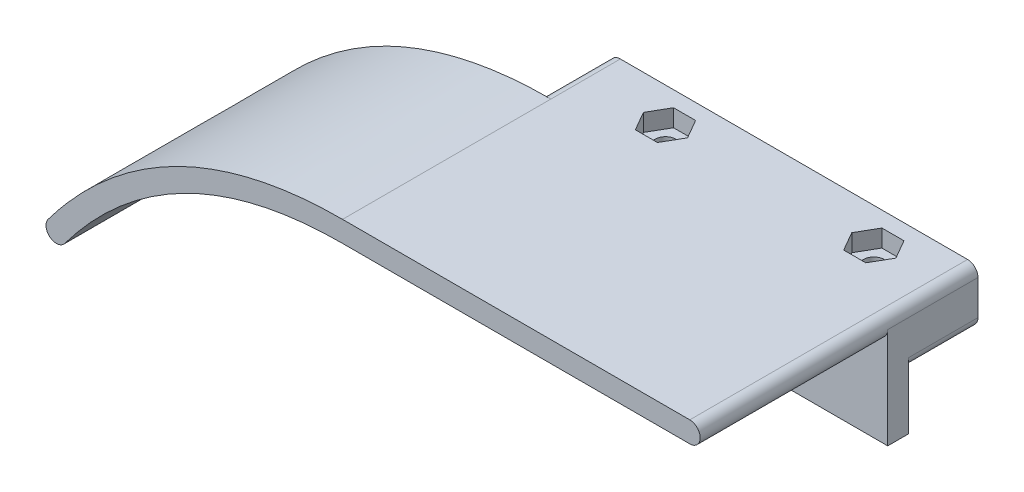
SolidWorks part; units mm, degrees
ref_plane "前视基准面" through (0, 0, 0) normal (0, 0, 1) x (1, 0, 0)
ref_plane "上视基准面" through (0, 0, 0) normal (0, 1, 0) x (1, 0, 0)
ref_plane "右视基准面" through (0, 0, 0) normal (1, 0, 0) x (0, 0, -1)
sketch "草图1" plane through (0, 0, 0) normal (0, 0, 1) x (1, 0, 0)
  line L0 (-25, -1.5) -> (-50, -1.5) construction
  line L1 (-25, -1.5) -> (25, -1.5)
  line L2 (-25, -1.5) -> (-25, 1.5) construction
  line L4 (25, -1.5) -> (25, 1.5) construction
  line L5 (-25, -1.5) -> (25, 1.5) construction
  line L6 (-25, 1.5) -> (25, -1.5) construction
  line L7 (-50, -1.5) -> (-65, -21.5) construction
  line L8 (-25, 1.5) -> (25, 1.5)
  arc A0 (25, 1.5) -> (25, -1.5) centre (25, 0) cw
  arc A2 (-67.4, -19.7) -> (-65, -21.5) centre (-66.2, -20.6) ccw
  spline S0 degree 2 poles (-25, -1.5) (-50, -1.5) (-65, -21.5) knots 0 0 0 1 1 1
  spline S1 degree 1 poles (-25, 1.5) (-67.4, -19.7) knots 0 0 1 1 construction
  spline S2 degree 2 poles (-25, 1.5) (-34.8412, 1.5115) (-49.0088, -3.4823) (-61.5045, -11.8201) (-67.4, -19.7) knots 0 0 0 0.375 0.625 1 1 1
  point P0 (0, 0)
  dimension "D3" = 20
  dimension "D1" = 50
  dimension "D2" = 3
  dimension "D4" = 25
  dimension "D5" = 40
extrude "凸台-拉伸1" add sketch "草图1" along normal blind 30 contours L8 A0 L1 S0 A2 S2
sketch "草图2" plane through (0, 0, 0) normal (0, 0, -1) x (-1, 0, 0)
  line L0 (25, 1.5) -> (-25, 1.5) construction
  line L1 (25, 1.5) -> (-25, 1.5)
  line L2 (-26.5, 0) -> (-26.5, -22.1)
  line L3 (66.2, -22.1) -> (-26.5, -22.1)
  arc A0 (65, -21.5) -> (67.4, -19.7) centre (66.2, -20.6) ccw construction
  arc A1 (-25, 1.5) -> (-25, -1.5) centre (-25, 0) ccw construction
  arc A2 (66.2, -22.1) -> (67.4, -19.7) centre (66.2, -20.6) ccw
  arc A3 (-25, 1.5) -> (-26.5, 0) centre (-25, 0) ccw
  spline S0 degree 2 poles (-1644.9856, -2478.1381) (-209.195, 87.5308) (49.0088, -3.4823) (276.7427, -155.4382) (-914.3307, -2843.4975) knots -10.765594 -10.765594 -10.765594 0.375 0.625 11.765648 11.765648 11.765648 only from (25, 1.5) to (67.4, -19.7) construction
  spline S1 degree 2 poles (25, 1.5) (34.8412, 1.5115) (49.0088, -3.4823) (61.5045, -11.8201) (67.4, -19.7) knots 0 0 0 0.375 0.625 1 1 1
  point P11 (0, 0)
extrude "凸台-拉伸2" add sketch "草图2" against normal blind 3
sketch "草图3" plane through (0, 0, 0) normal (0, 0, -1) x (-1, 0, 0)
  line L0 (-25, 1.5) -> (25, 1.5)
  line L1 (-26.5, 0) -> (-26.5, -5)
  line L2 (-26.5, 0) -> (-26.5, -22.1) construction
  line L3 (26.5, 0) -> (26.5, -5)
  line L4 (-25, -6.5) -> (25, -6.5)
  arc A0 (-25, 1.5) -> (-26.5, 0) centre (-25, 0) ccw construction
  arc A1 (-26.5, -5) -> (-25, -6.5) centre (-25, -5) ccw
  arc A2 (25, -6.5) -> (26.5, -5) centre (25, -5) ccw
  arc A3 (26.5, 0) -> (25, 1.5) centre (25, 0) ccw
  arc A4 (-25, 1.5) -> (-26.5, 0) centre (-25, 0) ccw
  point P19 (0, 0)
  point P20 (-26.5, -2.0139)
  point P21 (0, 0)
  point P22 (0, 0)
  point P23 (0, 0)
  dimension "D1" = 8
extrude "凸台-拉伸3" add sketch "草图3" along normal blind 10
sketch "草图4" plane through (0, 1.5, 0) normal (0, 1, 0) x (1, 0, 0)
  line L0 (-25, 5) -> (-15.7274, 5) construction
  line L3 (-25, 10) -> (25, 10) construction
  line L4 (26.5, -3) -> (26.5, 10) construction
  circle A0 centre (-13.5, 5) radius 1.5
  circle A1 centre (16.5, 5) radius 1.5
  dimension "D1" = 5
  dimension "D2" = 3
  dimension "D3" = 30
  dimension "D4" = 10
extrude "切除-拉伸1" cut sketch "草图4" against normal through all contours A0 | A1
sketch "草图5" plane through (0, 0, 0) normal (0, 0, -1) x (-1, 0, 0)
  line L0 (-26.5, -14.5) -> (33.5, -14.5)
  line L1 (-26.5, -5) -> (-26.5, -22.1) construction
  line L2 (-26.5, -22.1) -> (66.2, -22.1) construction
  line L3 (-25, -6.5) -> (25, -6.5) construction
  line L4 (-26.5, -14.5) -> (-26.5, -22.1)
  line L5 (-26.5, -22.1) -> (41.1, -22.1)
  arc A0 (33.5, -14.5) -> (41.1, -22.1) centre (33.5, -22.1) cw
  dimension "D1" = 8
  dimension "D2" = 60
extrude "切除-拉伸2" cut sketch "草图5" against normal through all
sketch "草图6" plane through (0, 1.5, 0) normal (0, 1, 0) x (1, 0, 0)
  line L1 (-11.9123, 7.75) -> (-15.0877, 7.75)
  line L2 (-15.0877, 7.75) -> (-16.6754, 5)
  line L3 (-16.6754, 5) -> (-15.0877, 2.25)
  line L4 (-15.0877, 2.25) -> (-11.9123, 2.25)
  line L5 (-11.9123, 2.25) -> (-10.3246, 5)
  line L6 (-10.3246, 5) -> (-11.9123, 7.75)
  line L7 (18.0877, 7.75) -> (14.9123, 7.75)
  line L8 (14.9123, 7.75) -> (13.3246, 5)
  line L9 (13.3246, 5) -> (14.9123, 2.25)
  line L10 (14.9123, 2.25) -> (18.0877, 2.25)
  line L11 (18.0877, 2.25) -> (19.6754, 5)
  line L12 (19.6754, 5) -> (18.0877, 7.75)
  circle A0 centre (-13.5, 5) radius 2.75 construction
  circle A1 centre (16.5, 5) radius 2.75 construction
  dimension "D1" = 5.5
extrude "切除-拉伸3" cut sketch "草图6" along normal through all from offset 2.5 offset against normal yes
fillet "圆角1" radius 2 1 edges at (-41.1, -22.1, 1.5)
